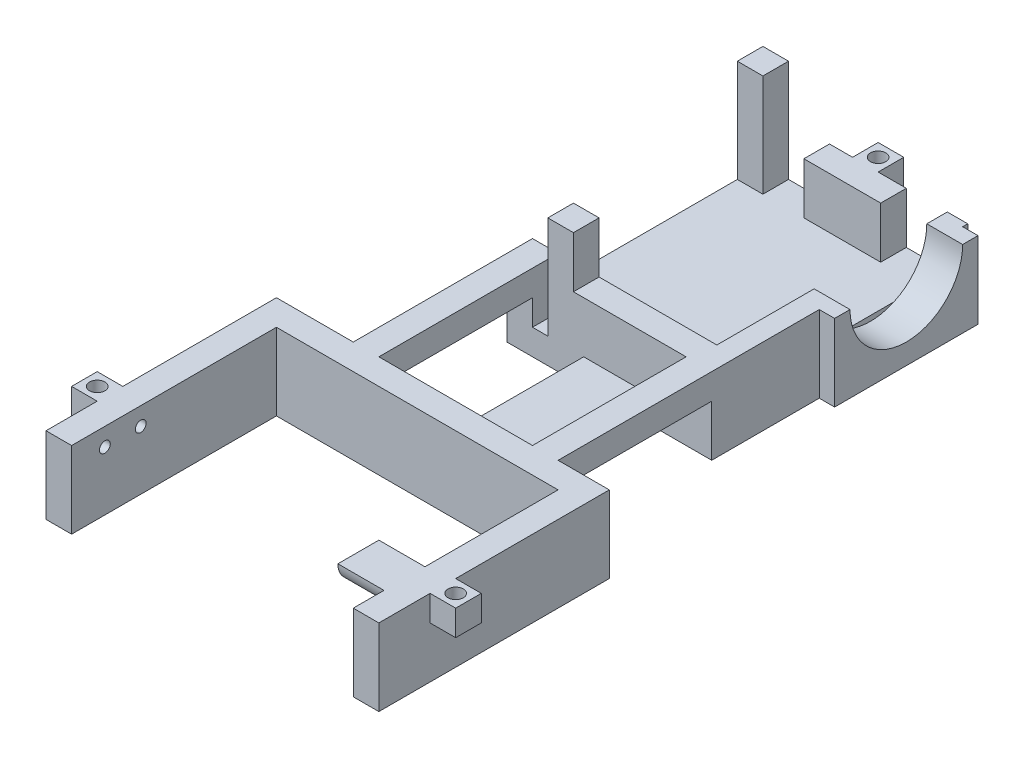
SolidWorks part; units mm, degrees
ref_plane "Front Plane" through (0, 0, 0) normal (0, 0, 1) x (1, 0, 0)
ref_plane "Top Plane" through (0, 0, 0) normal (0, 1, 0) x (1, 0, 0)
ref_plane "Right Plane" through (0, 0, 0) normal (1, 0, 0) x (0, 0, -1)
sketch "Sketch1" plane through (0, 0, 0) normal (0, 1, 0) x (1, 0, 0)
  line L1 (-20, 25) -> (20, 25)
  line L2 (-20, 25) -> (-20, -25)
  line L3 (-20, -25) -> (20, -25)
  line L4 (20, 25) -> (20, -25)
  point P5 (-20, 0)
  point P6 (0, 25)
  dimension "D1" = 40
  dimension "D2" = 50
extrude "Boss-Extrude1" add sketch "Sketch1" along normal blind 5
sketch "Sketch4" plane through (0, 5, 0) normal (0, 1, 0) x (1, 0, 0)
  line L0 (-20, -25) -> (20, -25) construction
  line L1 (20, 25) -> (16, 25)
  line L2 (20, 25) -> (20, -25)
  line L4 (16, 25) -> (16, -20)
  line L5 (20, 25) -> (-20, 25) construction
  line L8 (16, -20) -> (-7, -20)
  line L9 (-7, -25) -> (-7, -20)
  line L10 (-20, 25) -> (-15, 25)
  line L11 (-20, 25) -> (-20, 20)
  line L12 (-20, 20) -> (-15, 20)
  line L13 (-15, 25) -> (-15, 20)
  line L14 (-7, 25) -> (8, 25)
  line L15 (-7, 25) -> (-7, 20)
  line L16 (-7, 20) -> (8, 20)
  line L17 (8, 25) -> (8, 20)
  line L18 (-7, -25) -> (20, -25)
  line L19 (-12, 25) -> (-12, 20) construction
  line L20 (-12, 20) -> (-7, 20) construction
  line L21 (-15, -20) -> (-15, -25)
  line L22 (-15, -20) -> (-20, -20)
  line L24 (-15, -25) -> (-15, -20) construction
  line L25 (-7, -20) -> (-12, -20)
  line L26 (-7, -20) -> (-7, -25)
  line L27 (-7, -25) -> (-12, -25)
  line L28 (-12, -20) -> (-12, -25)
  line L29 (-20, 25) -> (-20, -25) construction
  line L30 (-20, -20) -> (-15, -20) construction
  line L31 (-20, -20) -> (-20, -25)
  line L32 (-20, -25) -> (-15, -25)
  line M19 (-20, 25) -> (-20, -25)
  line M20 (-20, -25) -> (20, -25)
  line M21 (20, -25) -> (20, 25)
  line M22 (20, 25) -> (-20, 25)
  dimension "D1" = 4
  dimension "D2" = 5
  dimension "D3" = 5
  dimension "D4" = 15
  dimension "D5" = 5
  dimension "D6" = 8
extrude "Boss-Extrude4" add sketch "Sketch4" along normal blind 20 contours L25 L28 L9 M20 | L13 L12 M22 M19 region at (-9.5, 5, 22.5) region at (-17.5, 5, -22.5)
extrude "Boss-Extrude5" add sketch "Sketch4<4>" along normal blind 10 contours L9 L4 L8 M20 M21 M22 | L17 L15 L16 M22 | L32 L21 L22 L31 region at (19.4318, 5, 0) region at (0.5, 5, -22.5)
sketch "Sketch4<4>" plane through (0, 5, 0) normal (0, 1, 0) x (1, 0, 0) same geometry as "Sketch4"
sketch "Sketch7" plane through (20, 0, 0) normal (1, 0, 0) x (0, 0, -1)
  line L0 (-25, 15) -> (25, 15) construction
  line L1 (-1, 15) -> (21, 15)
  arc A0 (-1, 15) -> (21, 15) centre (10, 15) ccw
  dimension "D1" = 22
extrude "Cut-Extrude2" cut sketch "Sketch7" against normal blind 4
sketch "Sketch8" plane through (20, 0, 0) normal (1, 0, 0) x (0, 0, -1)
  line L0 (-1, 15) -> (-4, 15)
  line L1 (-25, 15) -> (-1, 15) construction
  line L2 (-4, 15) -> (-4, 0)
  line L3 (-25, 0) -> (25, 0) construction
  line L4 (-4, 0) -> (24, 0)
  line L5 (24, 0) -> (24, 15)
  line L6 (21, 15) -> (25, 15) construction
  line L7 (24, 15) -> (21, 15)
  arc A0 (-1, 15) -> (21, 15) centre (10, 15) ccw
  dimension "D2" = 22
  dimension "D1" = 3
extrude "Boss-Extrude7" add sketch "Sketch8" along normal blind 3
sketch "Sketch10" plane through (0, 0, -25) normal (0, 0, -1) x (-1, 0, 0)
  line L0 (-8, 15) -> (7, 15) construction
  line L1 (-2.5, 15) -> (2.5, 15)
  line L2 (-2.5, 15) -> (-2.5, 10)
  line L3 (-2.5, 10) -> (2.5, 10)
  line L4 (2.5, 15) -> (2.5, 10)
  line L5 (-20, 0) -> (20, 0) construction
  point P8 (0, 0)
  point P9 (0, 10)
  dimension "D1" = 5
  dimension "D2" = 5
extrude "Boss-Extrude9" add sketch "Sketch10" along normal blind 5
sketch "Sketch11" plane through (0, 10, 0) normal (0, -1, 0) x (1, 0, 0)
  line L0 (2.5, -30) -> (-2.5, -30) construction
  line L1 (2.5, -30) -> (2.5, -25) construction
  circle A0 centre (0, -27.5) radius 1.5
  point P4 (0, -30)
  point P7 (2.5, -27.5)
  dimension "D1" = 3
extrude "Cut-Extrude3" cut sketch "Sketch11" against normal blind 5
sketch "Sketch12" plane through (0, 0, 25) normal (0, 0, 1) x (1, 0, 0)
  line L0 (-20, 15) -> (-20, 0) construction
  line L1 (-15, 15) -> (-20, 15)
  line L2 (-15, 15) -> (-15, 10)
  line L3 (-15, 10) -> (-20, 10)
  line L4 (-20, 15) -> (-20, 10)
  line L5 (-20, 0) -> (20, 0) construction
  line L6 (20, 15) -> (15, 15)
  line L7 (20, 15) -> (20, 10)
  line L8 (20, 10) -> (15, 10)
  line L9 (15, 15) -> (15, 10)
  line L10 (-5, 0) -> (5, 0)
  line L11 (-5, 0) -> (-5, 5)
  line L12 (-5, 5) -> (5, 5)
  line L13 (5, 0) -> (5, 5)
  point P18 (0, 5)
  dimension "D1" = 5
  dimension "D2" = 5
  dimension "D3" = 10
extrude "Boss-Extrude10" add sketch "Sketch12" along normal blind 30
sketch "Sketch13" plane through (0, 0, 55) normal (0, 0, 1) x (1, 0, 0)
  line L0 (-20, 15) -> (-20, 10) construction
  line L1 (20, 0) -> (-20, 0)
  line L2 (20, 0) -> (20, 15)
  line L3 (20, 15) -> (-20, 15)
  line L4 (-20, 0) -> (-20, 15)
  line L5 (-5, 0) -> (5, 0) construction
  point P6 (0, 0)
extrude "Boss-Extrude11" add sketch "Sketch13" along normal blind 5
sketch "Sketch14" plane through (20, 0, 0) normal (1, 0, 0) x (0, 0, -1)
  line L1 (-55, 0) -> (-60, 0)
  line L2 (-55, 0) -> (-55, 15)
  line L3 (-55, 15) -> (-60, 15)
  line L4 (-60, 0) -> (-60, 15)
extrude "Boss-Extrude12" add sketch "Sketch14" along normal blind 10
sketch "Sketch15" plane through (-20, 0, 0) normal (-1, 0, 0) x (0, 0, 1)
  line L1 (55, 0) -> (60, 0)
  line L2 (55, 0) -> (55, 15)
  line L3 (55, 15) -> (60, 15)
  line L4 (60, 0) -> (60, 15)
extrude "Boss-Extrude13" add sketch "Sketch15" along normal blind 15
sketch "Sketch16" plane through (0, 0, 60) normal (0, 0, 1) x (1, 0, 0)
  line L0 (-35, 0) -> (30, 0) construction
  line L1 (-35, 15) -> (-30, 15)
  line L2 (-35, 15) -> (-35, 0)
  line L3 (-35, 0) -> (-30, 0)
  line L4 (-30, 15) -> (-30, 0)
  line L6 (30, 15) -> (25, 15)
  line L7 (30, 15) -> (30, 0)
  line L8 (30, 0) -> (25, 0)
  line L9 (25, 15) -> (25, 0)
  dimension "D1" = 5
extrude "Boss-Extrude14" add sketch "Sketch16" along normal blind 40
sketch "Sketch17" plane through (25, 0, 0) normal (-1, 0, 0) x (0, 0, 1)
  line L0 (100, 15) -> (100, 0) construction
  line L1 (100, 15) -> (55, 15) construction
  line L2 (86, 15) -> (94, 15)
  arc A0 (86, 15) -> (94, 15) centre (90, 15) ccw
  dimension "D1" = 8
  dimension "D2" = 10
extrude "Boss-Extrude15" add sketch "Sketch17" along normal blind 9
sketch "Sketch18" plane through (-35, 0, 0) normal (-1, 0, 0) x (0, 0, 1)
  line L0 (100, 15) -> (100, 0) construction
  line L1 (85, 15) -> (90, 15)
  line L2 (85, 15) -> (85, 10)
  line L3 (85, 10) -> (90, 10)
  line L4 (90, 15) -> (90, 10)
  dimension "D1" = 5
  dimension "D2" = 5
  dimension "D3" = 10
extrude "Boss-Extrude16" add sketch "Sketch18" along normal blind 5
sketch "Sketch19" plane through (0, 10, 0) normal (0, -1, 0) x (1, 0, 0)
  line L0 (-40, 90) -> (-35, 90) construction
  line L1 (-40, 85) -> (-40, 90) construction
  circle A0 centre (-37.5, 87.5) radius 1.5
  point P2 (0, 0)
  point P5 (-37.5, 90)
  point P8 (-40, 87.5)
  dimension "D1" = 3
extrude "Cut-Extrude4" cut sketch "Sketch19" against normal blind 5
sketch "Sketch20" plane through (30, 0, 0) normal (1, 0, 0) x (0, 0, -1)
  line L0 (-55, 15) -> (-100, 15) construction
  line L1 (-85, 10) -> (-90, 10)
  line L2 (-85, 10) -> (-85, 15)
  line L3 (-85, 15) -> (-90, 15)
  line L4 (-90, 10) -> (-90, 15)
  line L5 (-100, 0) -> (-100, 15) construction
  dimension "D1" = 5
  dimension "D2" = 5
  dimension "D3" = 10
extrude "Boss-Extrude17" add sketch "Sketch20" along normal blind 5
sketch "Sketch21" plane through (0, 10, 0) normal (0, -1, 0) x (1, 0, 0)
  line L0 (35, 90) -> (35, 85) construction
  line L1 (35, 90) -> (30, 90) construction
  circle A0 centre (32.5, 87.5) radius 1.5
  point P4 (35, 87.5)
  point P7 (32.5, 90)
  dimension "D1" = 3
extrude "Cut-Extrude5" cut sketch "Sketch21" against normal blind 5
sketch "Sketch24" plane through (-30, 0, 0) normal (1, 0, 0) x (0, 0, -1)
  line L0 (-90, 8) -> (-97, 15) construction
  line L1 (-100, 15) -> (-60, 15) construction
  line L2 (-90, 15) -> (-83, 15) construction
  line L3 (-90, 15) -> (-90, 8) construction
  line L4 (-90, 8) -> (-83, 15) construction
  line L5 (-90, 15) -> (-97, 15) construction
  circle A0 centre (-93.5, 11.5) radius 1.05
  circle A1 centre (-86.5, 11.5) radius 1.05
  point P0 (-93.5, 11.5)
  point P11 (-86.5, 11.5)
  point P12 (-90, 8)
  point P14 (-90, 15)
  point P16 (0, 0)
  dimension "D6" = 2.1
  dimension "D1" = 7
  dimension "D2" = 7
  dimension "D3" = 7
  dimension "D4" = 3
extrude "Cut-Extrude6" cut sketch "Sketch24" against normal blind 5
